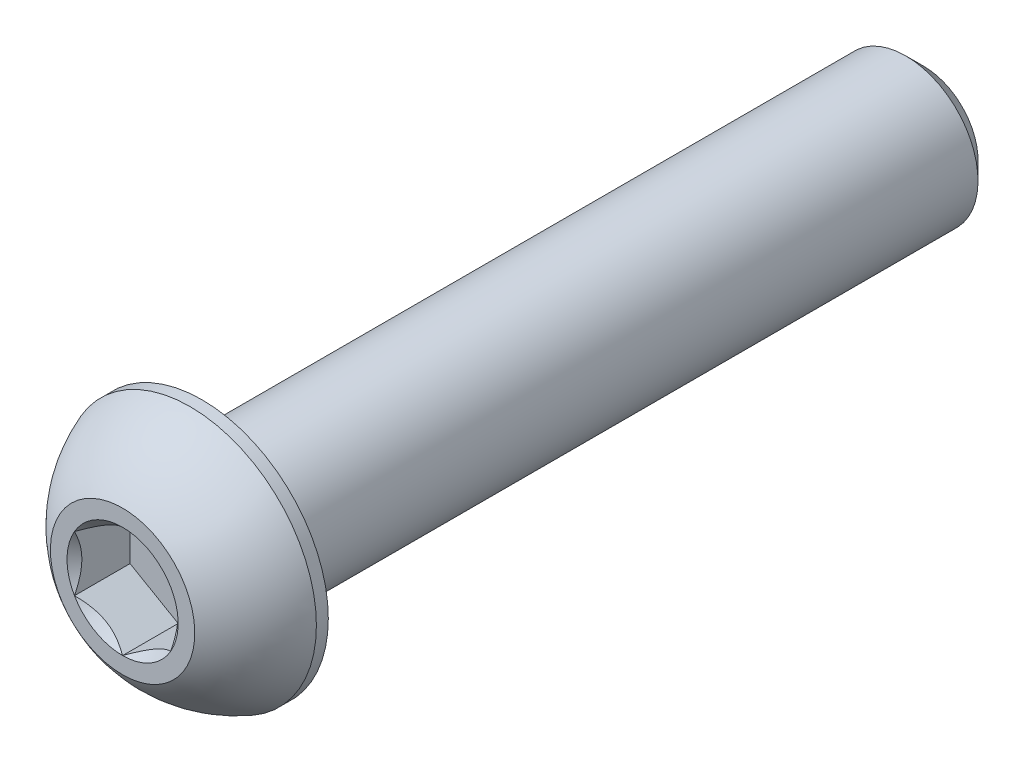
SolidWorks part; units mm, degrees
material "Alloy Steel"
ref_plane "Front" through (0, 0, 0) normal (0, 0, 1) x (1, 0, 0)
ref_plane "Top" through (0, 0, 0) normal (0, 1, 0) x (1, 0, 0)
ref_plane "Right" through (0, 0, 0) normal (1, 0, 0) x (0, 0, -1)
sketch "Sketch1" plane through (0, 0, 0) normal (1, 0, 0) x (0, 0, -1)
  line L2 (3.3, 3) -> (33.3, 3)
  line L3 (33.3, 3) -> (33.3, 0)
  line L4 (33.3, 0) -> (3.3, 0)
  line L6 (2.805, 5.25) -> (3.3, 5.25) construction
  line L7 (33.3, 3) -> (33.3, -3) construction
  line L8 (0, 0) -> (3.3, 0) construction
  line L9 (3.3, 5.25) -> (3.3, -5.25) construction
  line L11 (3.3, 3) -> (3.3, 0)
  line L13 (0, 2) -> (0, -2) construction
  line L14 (0, 2) -> (0, 3) construction
  line L15 (33.3, 3) -> (33.3, 2) construction
  line L16 (33.2375, 3.1083) -> (33.7375, 2.2422) construction
  line L17 (33.7375, 2.2422) -> (34.2375, 3.1083) construction
  line L18 (34.2375, 3.1083) -> (33.2375, 3.1083) construction
  line L19 (33.7375, 2.2422) -> (33.7375, 2.3505) construction
  line L20 (33.675, 2.3505) -> (33.8, 2.3505) construction
  line L21 (33.7375, 3.1083) -> (33.7375, 3) construction
  line L22 (34.175, 3) -> (33.3, 3) construction
  line L23 (33.7375, 3.0541) -> (34.2062, 3.0541) construction
  line L24 (33.7375, 3.0541) -> (33.2687, 3.0541) construction
  arc A3 (0, 3) -> (2.805, 5.25) centre (4.7113, 0) cw construction
  point P27 (30.8, -3)
  dimension "Dia" = 6
  dimension "D1" = 0.495
  dimension "Head Ht" = 3.3
  dimension "Head Dia" = 10.5
  dimension "Lg" = 30
  dimension "Hex" = 4
  dimension "Pitch" = 1
  dimension "D2" = 1
  dimension "D3" = 0.125
  dimension "D4" = 2.5
revolve "Revolve1" add sketch "Sketch1" angle 360 mid plane about L4
sketch "Sketch3" [suppressed] plane through (0, 0, -33.3) normal (0, 0, -1) x (-1, 0, 0)
  circle A0 centre (0, 0) radius 3
chamfer "Chamfer1" distance 0.75 angle 45 1 edges at (0, 3, -33.3)
sketch "Sketch7" plane through (0, 0, 0) normal (1, 0, 0) x (0, 0, -1)
  line L6 (2.805, 5.25) -> (3.3, 5.25) construction
  line L8 (0, 0) -> (3.3, 0) construction
  line L11 (3.3, 5.25) -> (3.3, -5.25) construction
  line L12 (2.805, 5.25) -> (3.3, 5.25)
  line L13 (0, 0) -> (3.3, 0)
  line L14 (0, 2) -> (0, -2) construction
  line L15 (3.3, 5.25) -> (3.3, 0)
  line L16 (0, 3) -> (0, 0)
  arc A2 (2.805, 5.25) -> (0, 3) centre (4.7113, 0) ccw construction
  arc A3 (2.805, 5.25) -> (0, 3) centre (4.7113, 0) ccw
revolve "Revolve2" add sketch "Sketch7" angle 360 mid plane about L13
sketch "Sketch5" plane through (0, 0, 0) normal (0, 0, 1) x (1, 0, 0)
  line L1 (2, -1.1547) -> (2, 1.1547)
  line L2 (2, 1.1547) -> (0, 2.3094)
  line L3 (0, 2.3094) -> (-2, 1.1547)
  line L4 (-2, 1.1547) -> (-2, -1.1547)
  line L5 (-2, -1.1547) -> (0, -2.3094)
  line L6 (0, -2.3094) -> (2, -1.1547)
  circle A0 centre (0, 0) radius 2 construction
extrude "Cut-Extrude2" cut sketch "Sketch5" against normal blind 2.31
sketch "Sketch6" plane through (0, 0, 0) normal (0, 0, 1) x (1, 0, 0)
  circle A0 centre (0, 0) radius 2.3094
extrude "Cut-Extrude3" cut sketch "Sketch6" against normal blind 2.31 draft 45
sketch "Sketch10" plane through (0, 0, 0) normal (1, 0, 0) x (0, 0, -1)
  line L0 (33.3, 3) -> (33.3, -3) construction
  point P0 (30.3, -3)
  dimension "D1" = 3
ref_axis "Center Axis 1" through (0, 0, -41.4782) along (0, 0, 1)
split "Split1" [suppressed] bodies to split 113
curve "Helix/Spiral2" [suppressed] pitch 1 height 31 turns 31
sketch "Sketch13" [suppressed] plane through (0, 0, 0) normal (1, 0, 0) x (0, 0, -1)
  line L0 (33.675, 2.3505) -> (33.2687, 3.0541)
  line L1 (33.675, 2.3505) -> (33.8, 2.3505)
  line L2 (33.2687, 3.0541) -> (34.2062, 3.0541)
  line L3 (34.2062, 3.0541) -> (33.8, 2.3505)
sweep "Cut-Sweep1" [suppressed] cut profiles "Sketch13" path "Helix/Spiral2"
sketch "Sketch14" [suppressed] plane through (0, 0, -3.3) normal (0, 0, -1) x (-1, 0, 0)
  circle A2 centre (0, 0) radius 3
  point P0 (0, 3)
extrude "Boss-Extrude1" [suppressed] add sketch "Sketch14" along normal up to next draft 20
equation "\"D1@Chamfer1\"=\"Pitch@Sketch1\"*0.75"
equation "\"D1@Cut-Extrude2\" = \"Head Ht@Sketch1\" * .7"
equation "\"D1@Sketch1\" = \"Head Ht@Sketch1\" * .15"
equation "\"D1@Cut-Extrude3\" = \"D1@Cut-Extrude2\""
equation "\"D3@Helix/Spiral2\"=\"Lg@Sketch1\"+\"Pitch@Sketch1\""
equation "\"D4@Helix/Spiral2\"=\"Pitch@Sketch1\""
equation "\"D2@Sketch1\"=\"Pitch@Sketch1\""
equation "\"D3@Sketch1\"=\"Pitch@Sketch1\"/8"
equation "\"D4@Sketch1\"=\"Pitch@Sketch1\"*2.5"
